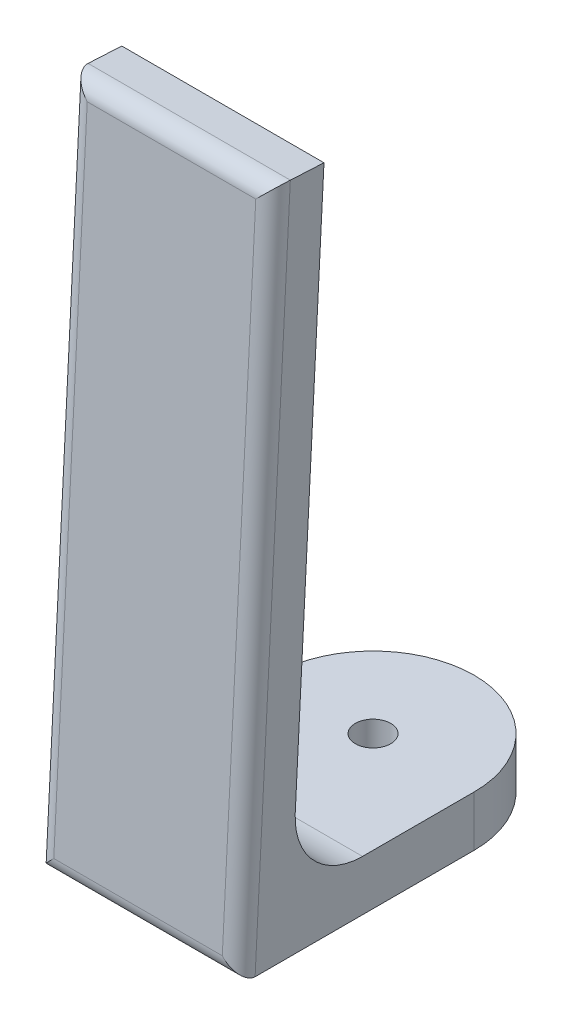
SolidWorks part; units mm, degrees
ref_plane "前视基准面" through (0, 0, 0) normal (0, 0, 1) x (1, 0, 0)
ref_plane "上视基准面" through (0, 0, 0) normal (0, 1, 0) x (1, 0, 0)
ref_plane "右视基准面" through (0, 0, 0) normal (1, 0, 0) x (0, 0, -1)
other "Configuration Table"
sketch "草图1" plane through (0, 0, 0) normal (1, 0, 0) x (0, 0, -1)
  line L0 (2.0934, 39.9452) -> (0, 0)
  line L1 (0, 0) -> (20, 0)
  line L2 (20, 0) -> (20, 3)
  line L3 (20, 3) -> (3.1613, 3)
  line L4 (3.1613, 3) -> (5.0893, 39.7882)
  line L5 (5.0893, 39.7882) -> (2.0934, 39.9452)
  dimension "D1" = 40
  dimension "D2" = 20
  dimension "D3" = 3
  dimension "D4" = 3
  dimension "D5" = 87
extrude "凸台-拉伸1" add sketch "草图1" along normal blind 12
sketch "草图2" plane through (0, 3, 0) normal (0, 1, 0) x (1, 0, 0)
  line L0 (6, 20) -> (6, 5.3368) construction
  line L2 (12, 20) -> (0, 20) construction
  circle A0 centre (6, 14) radius 1.05
  point P3 (6, 14.1105)
  point P5 (6, 14.1565)
  dimension "D1" = 2.1
  dimension "D2" = 6
extrude "切除-拉伸1" cut sketch "草图2" against normal blind 12
fillet "圆角1" radius 1 4 edges at (6, 39.9452, -2.0934) (12, 19.9726, -1.0467) (6, 0, 0) (0, 19.9726, -1.0467)
fillet "圆角2" radius 6 2 edges at (0, 1.5, -20) (12, 1.5, -20)
fillet "圆角3" radius 4 1 edges at (6, 3, -3.1613)
